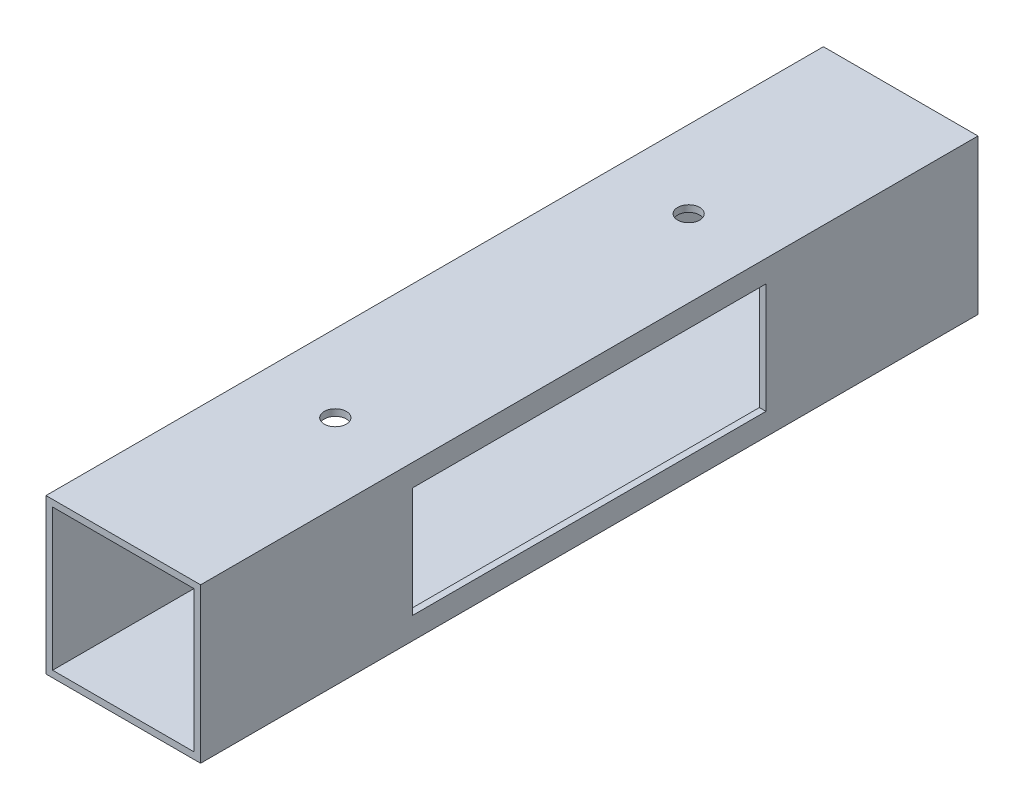
SolidWorks part; units mm, degrees
ref_plane "Plan de face" through (0, 0, 0) normal (0, 0, 1) x (1, 0, 0)
ref_plane "Plan de dessus" through (0, 0, 0) normal (0, 1, 0) x (1, 0, 0)
ref_plane "Plan de droite" through (0, 0, 0) normal (1, 0, 0) x (0, 0, -1)
sketch "MotorBlockSketch" plane through (0, 0, 0) normal (0, 0, 1) x (1, 0, 0)
  line L1 (-17.5, -17.5) -> (17.5, -17.5)
  line L2 (-17.5, -17.5) -> (-17.5, 17.5)
  line L3 (-17.5, 17.5) -> (17.5, 17.5)
  line L4 (17.5, -17.5) -> (17.5, 17.5)
  line L5 (-16, -16) -> (16, -16)
  line L6 (-16, -16) -> (-16, 16)
  line L7 (-16, 16) -> (16, 16)
  line L8 (16, -16) -> (16, 16)
  dimension "D1" = 35
  dimension "D2" = 35
  dimension "D3" = 1.5
  dimension "D4" = 1.5
  dimension "D5" = 32
  dimension "D6" = 17.5
  dimension "D7" = 17.5
extrude "Boss.-Extru.1" add sketch "MotorBlockSketch" along normal mid plane 176
sketch "Esquisse3" plane through (17.5, 0, 0) normal (1, 0, 0) x (0, 0, -1)
  line L0 (-88, 17.5) -> (88, 17.5) construction
  line L1 (-40, 12.5) -> (40, 12.5)
  line L2 (-40, 12.5) -> (-40, -12.5)
  line L3 (-40, -12.5) -> (40, -12.5)
  line L4 (40, 12.5) -> (40, -12.5)
  line L5 (-88, -17.5) -> (88, -17.5) construction
  line L7 (0, 55) -> (0, -55) construction
  dimension "D1" = 80
  dimension "D2" = 5
  dimension "D3" = 5
  dimension "D4" = 40
extrude "Enlèv. mat.-Extru.1" cut sketch "Esquisse3" against normal through all
sketch "DrillLeftMotorFixSketch" plane through (0, 17.5, 0) normal (0, 1, 0) x (1, 0, 0)
  line L0 (-19.25, 0) -> (19.25, 0) construction
  circle A0 centre (0, 40) radius 2.5
  dimension "D1" = 5
  dimension "D2" = 40
extrude "Enlèv. mat.-Extru.2" cut sketch "DrillLeftMotorFixSketch" against normal blind 5
sketch "DrillRightMotorFixSketch" plane through (0, 17.5, 0) normal (0, 1, 0) x (1, 0, 0)
  line L2 (0, -19.25) -> (0, 19.25) construction
  circle A0 centre (0, -40) radius 2.5
  dimension "D1" = 5
  dimension "D2" = 40
extrude "Enlèv. mat.-Extru.3" cut sketch "DrillRightMotorFixSketch" against normal blind 5
